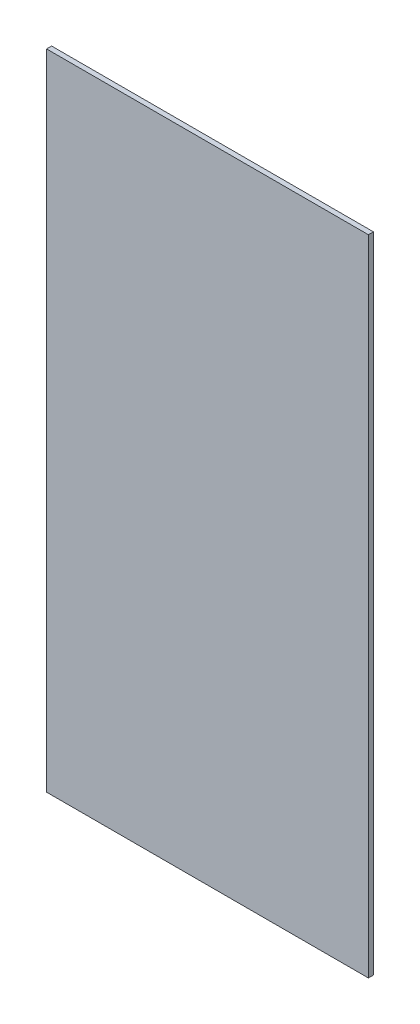
SolidWorks part; units mm, degrees
ref_plane "Front" through (0, 0, 0) normal (0, 0, 1) x (1, 0, 0)
ref_plane "Top" through (0, 0, 0) normal (0, 1, 0) x (1, 0, 0)
ref_plane "Right" through (0, 0, 0) normal (1, 0, 0) x (0, 0, -1)
sketch "Sketch1" plane through (0, 0, 0) normal (0, 0, 1) x (1, 0, 0)
  line L1 (-43.2328, -162.4203) -> (58.3672, -162.4203)
  line L2 (-43.2328, -162.4203) -> (-43.2328, 40.7797)
  line L3 (-43.2328, 40.7797) -> (58.3672, 40.7797)
  line L4 (58.3672, -162.4203) -> (58.3672, 40.7797)
  dimension "D1" = 101.6
  dimension "D2" = 203.2
extrude "Boss-Extrude1" add sketch "Sketch1" along normal blind 1.5875
